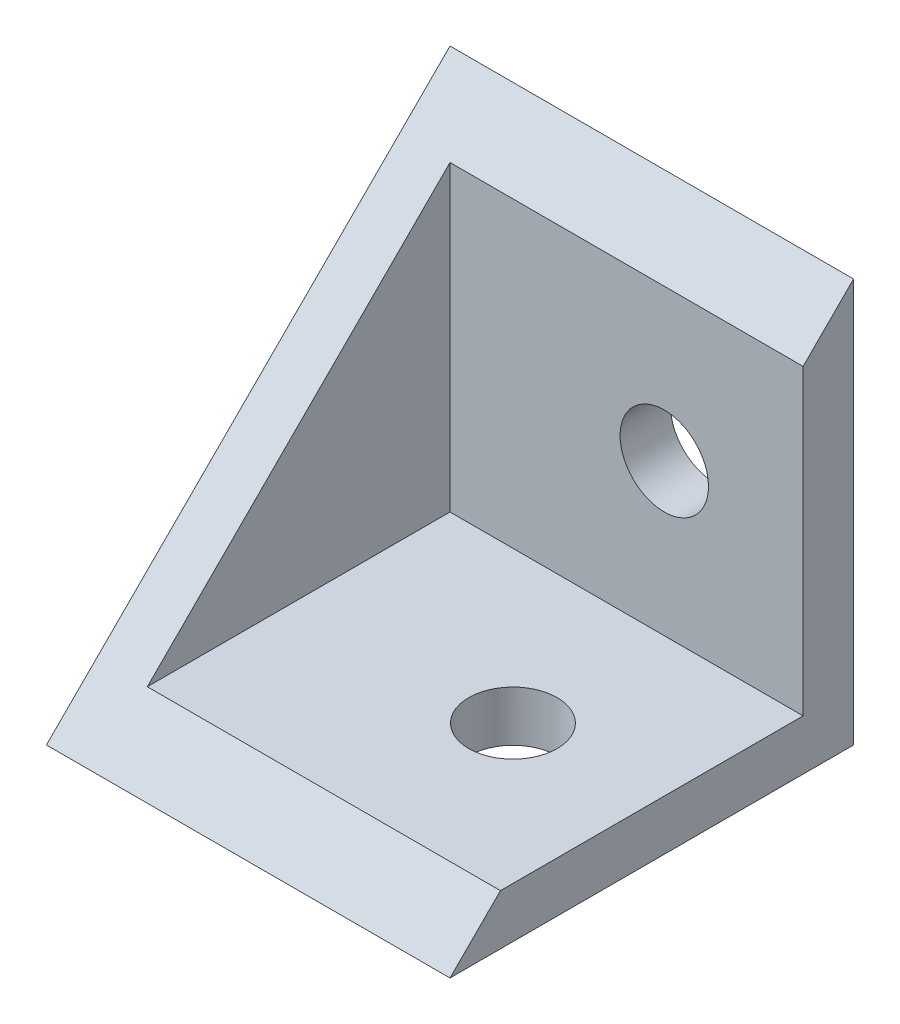
SolidWorks part; units mm, degrees
ref_plane "Front Plane" through (0, 0, 0) normal (0, 0, 1) x (1, 0, 0)
ref_plane "Top Plane" through (0, 0, 0) normal (0, 1, 0) x (1, 0, 0)
ref_plane "Right Plane" through (0, 0, 0) normal (1, 0, 0) x (0, 0, -1)
sketch "Sketch1" plane through (0, 0, 0) normal (0, 1, 0) x (1, 0, 0)
  line L1 (-12.7, -12.7) -> (12.7, -12.7)
  line L2 (-12.7, -12.7) -> (-12.7, 12.7)
  line L3 (-12.7, 12.7) -> (12.7, 12.7)
  line L4 (12.7, -12.7) -> (12.7, 12.7)
  line L5 (-12.7, -12.7) -> (12.7, 12.7) construction
  line L6 (-12.7, 12.7) -> (12.7, -12.7) construction
  point P0 (0, 0)
  dimension "D1" = 25.4
  dimension "D2" = 25.4
extrude "Boss-Extrude1" add sketch "Sketch1" along normal blind 25.4
sketch "Sketch2" plane through (12.7, 0, 0) normal (1, 0, 0) x (0, 0, -1)
  line L0 (-12.7, 25.4) -> (12.7, 25.4)
  line L1 (12.7, 25.4) -> (-12.7, 0)
  line L2 (-12.7, 0) -> (-12.7, 25.4)
extrude "Cut-Extrude1" cut sketch "Sketch2" against normal blind 25.4
sketch "Sketch3" plane through (12.7, 0, 0) normal (1, 0, 0) x (0, 0, -1)
  line L0 (-9.525, 3.175) -> (9.525, 3.175)
  line L1 (-12.7, 0) -> (12.7, 25.4) construction
  line L2 (9.525, 3.175) -> (9.525, 22.225)
  line L3 (-12.7, 0) -> (12.7, 0) construction
  line L4 (12.7, 25.4) -> (12.7, 0) construction
  dimension "D1" = 3.175
  dimension "D2" = 3.175
extrude "Cut-Extrude2" cut sketch "Sketch3" against normal blind 22.225 and the other way through all
sketch "Sketch4" plane through (0, 0, -9.525) normal (0, 0, 1) x (1, 0, 0)
  line L0 (12.7, 22.225) -> (12.7, 3.175) construction
  line L1 (-12.7, 0) -> (12.7, 0) construction
  circle A0 centre (3.9624, 12.7) radius 2.7813
  dimension "D1" = 5.5626
  dimension "D2" = 8.7376
  dimension "D3" = 12.7
extrude "Cut-Extrude3" cut sketch "Sketch4" against normal blind 22.225
sketch "Sketch5" plane through (0, 3.175, 0) normal (0, 1, 0) x (1, 0, 0)
  line L0 (12.7, 9.525) -> (12.7, -9.525) construction
  line L1 (12.7, 12.7) -> (-12.7, 12.7) construction
  circle A0 centre (3.9624, 0) radius 2.7813
  dimension "D1" = 5.5626
  dimension "D2" = 8.7376
  dimension "D3" = 12.7
extrude "Cut-Extrude4" cut sketch "Sketch5" against normal blind 22.225
